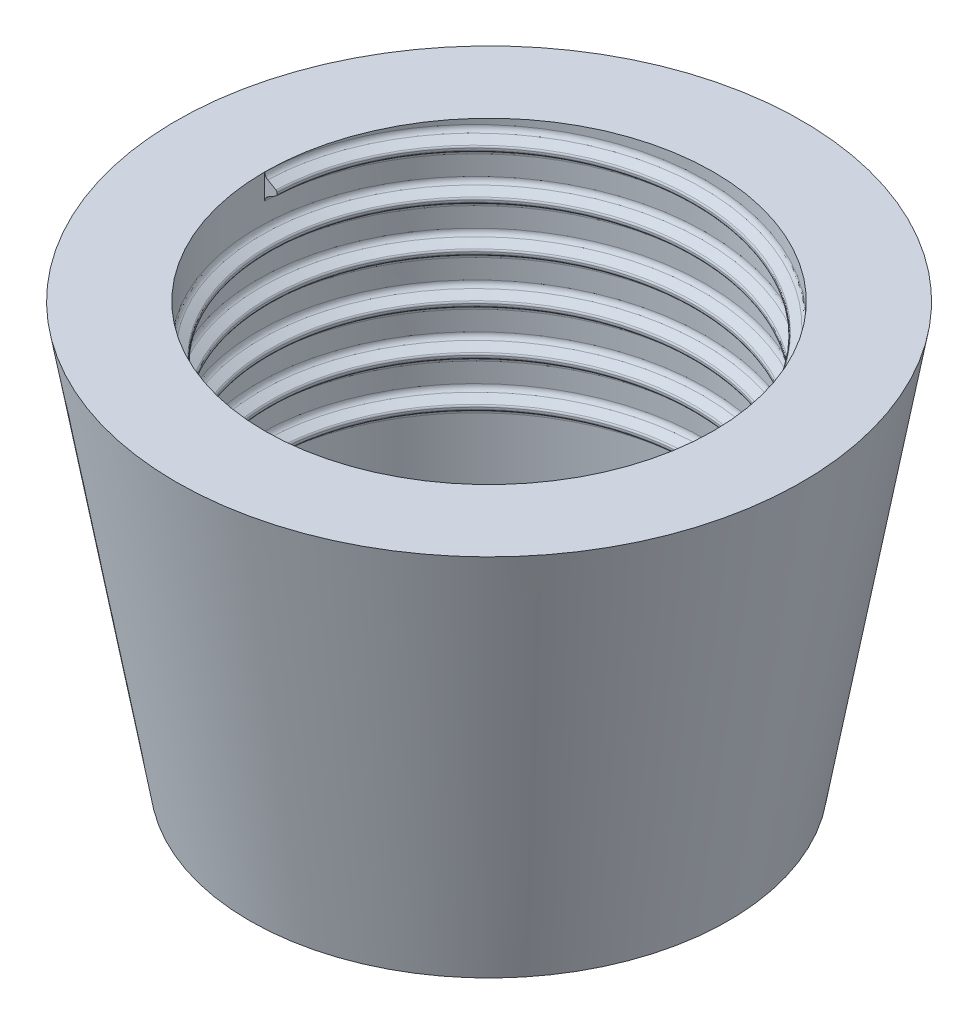
SolidWorks part; units mm, degrees
ref_plane "Front Plane" through (0, 0, 0) normal (0, 0, 1) x (1, 0, 0)
ref_plane "Top Plane" through (0, 0, 0) normal (0, 1, 0) x (1, 0, 0)
ref_plane "Right Plane" through (0, 0, 0) normal (1, 0, 0) x (0, 0, -1)
sketch "Sketch1" plane through (0, 0, 0) normal (0, 1, 0) x (1, 0, 0)
  circle A0 centre (0, 0) radius 16
extrude "Boss-Extrude1" add sketch "Sketch1" along normal blind 20 draft 10 contours A0 draft outward yes
sketch "Sketch2" plane through (0, 20, 0) normal (0, 1, 0) x (1, 0, 0)
  circle A0 centre (0, 0) radius 14
sketch "Sketch10" plane through (0, 20, 0) normal (0, 1, 0) x (1, 0, 0)
  circle A0 centre (0, 0) radius 14
extrude "Cut-Extrude2" cut sketch "Sketch10" against normal blind 20
thread "Thread1" pitch 2.1167 method extrude profile "Thread Profile2" start angle 0, offset 0, length 16, pitch 2.8, diameter 28
ref_plane "Plane2" through (-14, 20, 0) normal (0, 0, -1) x (1, 0, 0)
sketch "Thread Profile2" plane through (-14, 20, 0) normal (0, 0, -1) x (1, 0, 0)
  line L0 (0, 0) -> (0, 2.1167) construction
  line L1 (0, 0) -> (0, 1.5829)
  line L2 (0.381, 1.5829) -> (0.762, 1.5829) construction
  line L3 (0.762, 0.8497) -> (0.762, 0.7332)
  line L4 (0.6985, 0.9597) -> (0.1905, 1.253)
  line L5 (0.6985, 0.6232) -> (0.1905, 0.33)
  line L6 (0.381, 0) -> (0.762, 0) construction
  arc A0 (0.1905, 1.253) -> (0, 1.5829) centre (0.381, 1.5829) cw
  arc A1 (0.1905, 0.33) -> (0, 0) centre (0.381, 0) ccw
  arc A2 (0.762, 0.7332) -> (0.6985, 0.6232) centre (0.635, 0.7332) cw
  arc A3 (0.762, 0.8497) -> (0.6985, 0.9597) centre (0.635, 0.8497) ccw
  point P10 (0.762, 0.923)
  point P17 (0.762, 0.6599)
  point P18 (0, 1.363)
  point P19 (0, 0.22)
  point P20 (0, 0)
  dimension "RootFillet1" = 0.381
  dimension "RootFillet2" = 0.381
  dimension "CrestFillet2" = 0.127
  dimension "CrestFillet1" = 0.127
  dimension "Pitch" = 2.1167
  dimension "Angle1" = 30
  dimension "Angle2" = 30
  dimension "a" = 1.143
  dimension "b" = 0.762
  dimension "c" = 0.2631
sketch "Sketch19" plane through (0, 0, 0) normal (0, -1, 0) x (-1, 0, 0)
  circle A0 centre (0, 0) radius 13
  circle A1 centre (0, 0) radius 6.5
sketch "Sketch20" plane through (0, 0, 0) normal (0, -1, 0) x (1, 0, 0)
  circle A0 centre (0, 0) radius 16
  point P3 (0, 0)
extrude "Boss-Extrude3" add sketch "Sketch20" along normal blind 6 draft 10
extrude "Cut-Extrude3" cut sketch "Sketch19" along normal blind 1.5 contours A1
sketch "Sketch47" plane through (0, -1.5, 0) normal (0, 1, 0) x (1, 0, 0)
  circle A0 centre (0, 0) radius 0.75
extrude "Cut-Extrude10" cut sketch "Sketch47" against normal blind 4.5
sketch "Sketch49" plane through (0, -1.5, 0) normal (0, 1, 0) x (1, 0, 0)
  circle A0 centre (0, 0) radius 0.5
  circle A2 centre (2.25, 0) radius 0.75
sketch "Sketch50" plane through (0, -1.5, 0) normal (0, 1, 0) x (1, 0, 0)
  circle A0 centre (4.25, 0) radius 0.75
extrude "Cut-Extrude13" cut sketch "Sketch49" against normal blind 4.5
extrude "Cut-Extrude14" cut sketch "Sketch50" against normal blind 4.5
pattern_circular "CirPattern2" count 12 over 360 about axis through (0, -1.5, 0) along (0, 1, 0) of "Cut-Extrude14"
pattern_circular "CirPattern3" count 6 over 360 about axis through (0, -1.5, 0) along (0, 1, 0) of "Cut-Extrude13"
